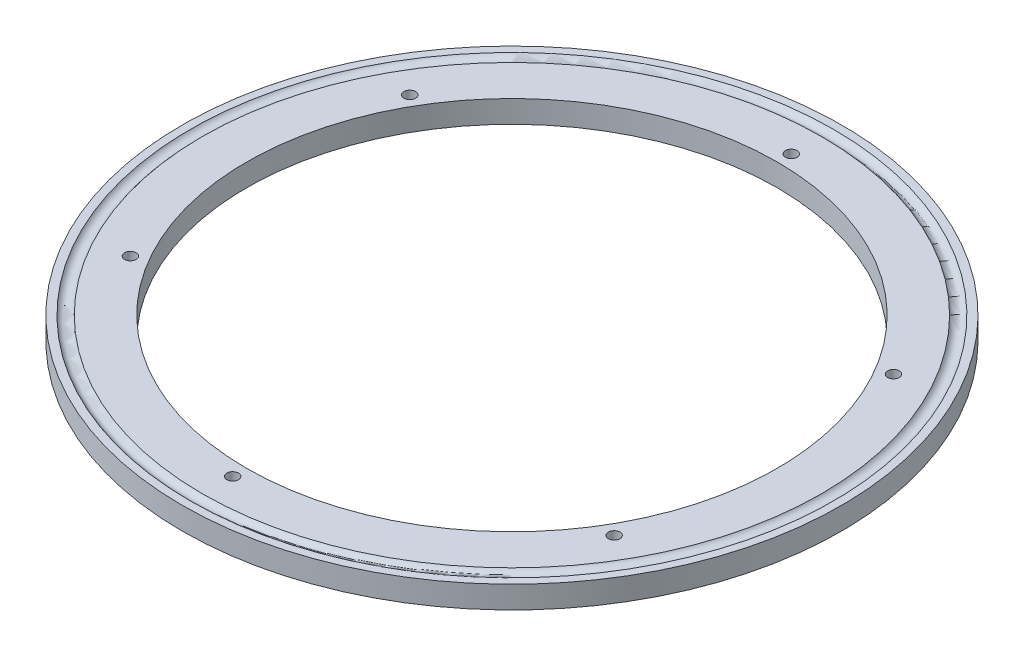
SolidWorks part; units mm, degrees
material "6061 Alloy"
ref_plane "Front Plane" through (0, 0, 0) normal (0, 0, 1) x (1, 0, 0)
ref_plane "Top Plane" through (0, 0, 0) normal (0, 1, 0) x (1, 0, 0)
ref_plane "Right Plane" through (0, 0, 0) normal (1, 0, 0) x (0, 0, -1)
sketch "Sketch1" plane through (0, 0, 0) normal (0, 1, 0) x (1, 0, 0)
  circle A0 centre (0, 0) radius 60.325
  circle A1 centre (0, 0) radius 74.93
  circle A2 centre (0, 0) radius 71.755
  circle A3 centre (0, -63.5) radius 1.3208
  circle A4 centre (-54.9926, -31.75) radius 1.3208
  circle A5 centre (-54.9926, 31.75) radius 1.3208
  circle A6 centre (0, 63.5) radius 1.3208
  circle A7 centre (54.9926, 31.75) radius 1.3208
  circle A8 centre (54.9926, -31.75) radius 1.3208
  point P21 (0, 0)
  dimension "D1" = 120.65
  dimension "D4" = 2.6416
  dimension "D5" = 63.5
  dimension "D2" = 14.605
  dimension "D3" = 11.43
  dimension "D6" = 6
extrude "Boss-Extrude1" add sketch "Sketch1" along normal blind 5.08 contours A2 A0 | A1 A2 region at (-72.8107, 0, 0) region at (-69.7255, 0, 0)
sketch "Sketch2" plane through (0, 0, 0) normal (1, 0, 0) x (0, 0, -1)
  line L0 (-74.93, 0) -> (74.93, 0) construction
  line L1 (74.93, 5.08) -> (-74.93, 5.08) construction
  line L2 (-74.93, 0) -> (74.93, 0)
  line L3 (74.93, 5.08) -> (-74.93, 5.08)
  line L4 (89.5975, 4.318) -> (99.9841, 4.318) construction
  line L5 (95.9885, 2.54) -> (99.6739, 2.54) construction
  line L6 (0, 0) -> (0, 18.217) construction
  circle A0 centre (71.755, 5.9055) radius 1.5875 construction
  circle A1 centre (71.755, 5.969) radius 1.651
  circle A2 centre (71.755, -0.889) radius 1.651
  dimension "D3" = 3.175
  dimension "D4" = 3.302
  dimension "D1" = 71.755
  dimension "D2" = 0.762
  dimension "D5" = 2.54
revolve "Cut-Revolve1" cut sketch "Sketch2" angle 360 about L6 region at (0, 0.3118, -71.755) region at (0, 4.7682, -71.755)
equation "\"Middle Coupler Inner Daimeter\"= 4.75in"
equation "\"Middle Coupler  Wall Thickness\" = 0.25in"
equation "\"Middle Coupler Bottom Thickness\"= 0.2in"
equation "\"Bearing Rail Offset\"= 0.45in"
equation "\"3-56 UNF Tap\"= 0.089in"
equation "\"3-56 UNF Clearance\"= 0.104in"
equation "\"D5@Sketch1\"=(\"Middle Coupler Inner Daimeter\"*2+0.5)/4in"
equation "\"Ball Bearing Distance\"= 0.03in"
equation "\"D1@Sketch2\"=\"Middle Coupler Inner Daimeter\"/2+\"Bearing Rail Offset\""
equation "\"D3@Sketch1\"=\"Bearing Rail Offset\""
equation "\"D4@Sketch1\"=\"3-56 UNF Clearance\""
equation "\"D1@Sketch1\"=\"Middle Coupler Inner Daimeter\""
equation "\"D2@Sketch2\"=\"Ball Bearing Distance\""
equation "\"D4@Sketch2\"=\"D3@Sketch2\"+0.005"
equation "\"D5@Sketch2\"=\"Middle Coupler Bottom Thickness\"/2"
equation "\"TCA Outer Diameter\" = 6.625in"
equation "\"Interstage Aeroframe Wall Thickness\" = 0.072in"
equation "\"Compression Spring OD\"= 0.42in"
equation "\"10-24 Tap\"= 0.157in"
equation "\"10-24 Clearance\"= 0.196in"
equation "\"Lower Stage Fuselage Wall Thickness\" = 0.25in"
equation "\"6-32 Tap\" = 0.107in"
equation "\"1/4-20 Tap\" = 0.201in"
